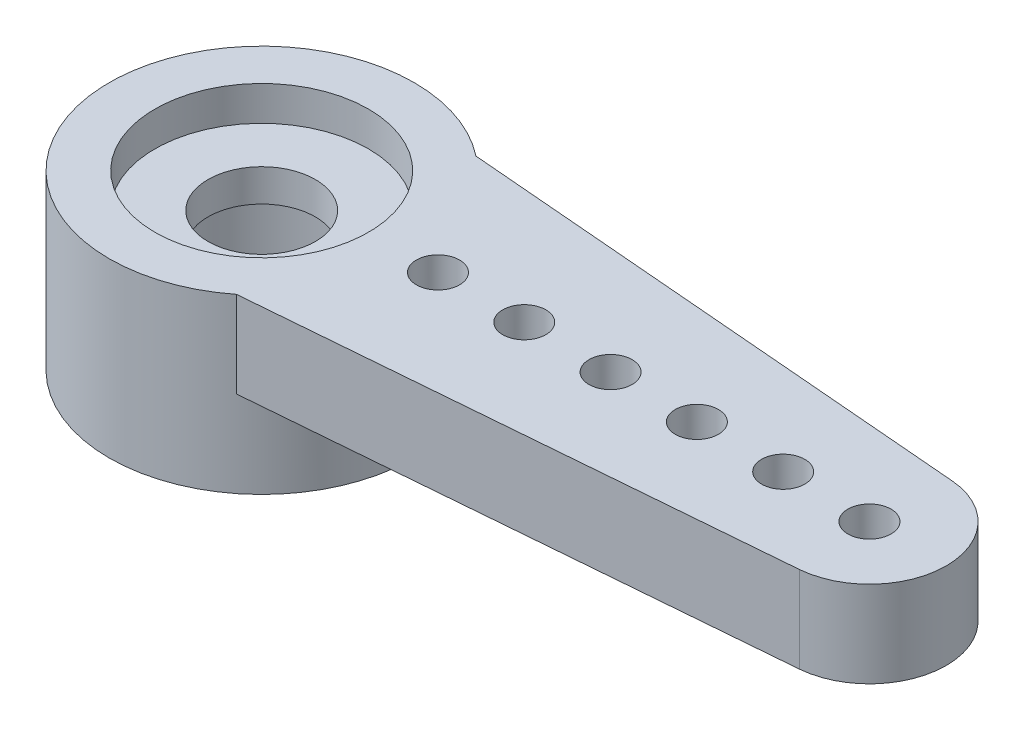
SolidWorks part; units mm, degrees
material "PA Type 6"
ref_plane "Front Plane" through (0, 0, 0) normal (0, 0, 1) x (1, 0, 0)
ref_plane "Top Plane" through (0, 0, 0) normal (0, 1, 0) x (1, 0, 0)
ref_plane "Right Plane" through (0, 0, 0) normal (1, 0, 0) x (0, 0, -1)
ref_axis "X-Axis" through (-88.99, 0, 0) along (1, 0, 0)
ref_axis "Y-Axis" through (0, 0, -88.99) along (0, 0, 1)
ref_axis "Z-Axis" through (0, 55, 0) along (0, -1, 0)
sketch "Sketch2" plane through (0, 0, 0) normal (0, 0, 1) x (1, 0, 0)
  line L0 (0, 0) -> (0, -2) construction
  line L1 (2.475, 2) -> (2.475, 1.2)
  line L2 (2.475, 1.2) -> (1.245, 1.2)
  line L3 (1.245, 1.2) -> (1.245, 0.45)
  line L4 (1.245, 0.45) -> (2.375, 0.45)
  line L5 (2.375, 0.45) -> (2.375, -2)
  line L6 (2.375, -2) -> (3.535, -2)
  line L7 (3.535, -2) -> (3.535, 2)
  line L8 (3.535, 2) -> (2.475, 2)
  dimension "D1" = 4.75
  dimension "D2" = 2.49
  dimension "D3" = 4.95
  dimension "D4" = 0.8
  dimension "D5" = 7.07
  dimension "D6" = 2
  dimension "D7" = 2.45
  dimension "D8" = 4
revolve "Revolve1" add sketch "Sketch2" angle 360 about axis through (0, 55, 0) along (0, -1, 0)
sketch "Sketch3" plane through (0, 0, 0) normal (0, 1, 0) x (1, 0, 0)
  line L0 (2.1899, -2.775) -> (14.2325, -1.7739)
  line L1 (0, 0) -> (20.2296, 0) construction
  line L2 (-3.535, 0) -> (15.865, 0) construction
  line L3 (2.1899, -2.775) -> (2.1899, 0)
  line L4 (2.1899, 0) -> (15.865, 0)
  circle A0 centre (0, 0) radius 3.535 construction
  circle A1 centre (14.085, 0) radius 1.78
  circle A2 centre (0, 0) radius 3.535
  circle A3 centre (14.085, 0) radius 0.5
  circle A4 centre (12.085, 0) radius 0.5
  circle A5 centre (10.085, 0) radius 0.5
  circle A6 centre (8.085, 0) radius 0.5
  circle A7 centre (6.085, 0) radius 0.5
  circle A8 centre (4.085, 0) radius 0.5
  circle A9 centre (0, 0) radius 2.475 construction
  dimension "D2" = 3.56
  dimension "D5" = 6
  dimension "D1" = 2.775
  dimension "D4" = 1
  dimension "D6" = 12.085
  dimension "D3" = 19.4
extrude "Boss-Extrude1" add sketch "Sketch3" along normal up to surface (2 mm away) contours A8 L4 A2 L0 A1 A4 A5 A6 A7 | A4 A1 L4 A3 region at (7.6377, 0, 1.3069) region at (14.1152, 0, 0.8137) up to face at (0, 2, 2.475)
mirror "Mirror1" about plane through (0, 15.9538, 0) normal (0, 0, -1) of "Boss-Extrude1"
